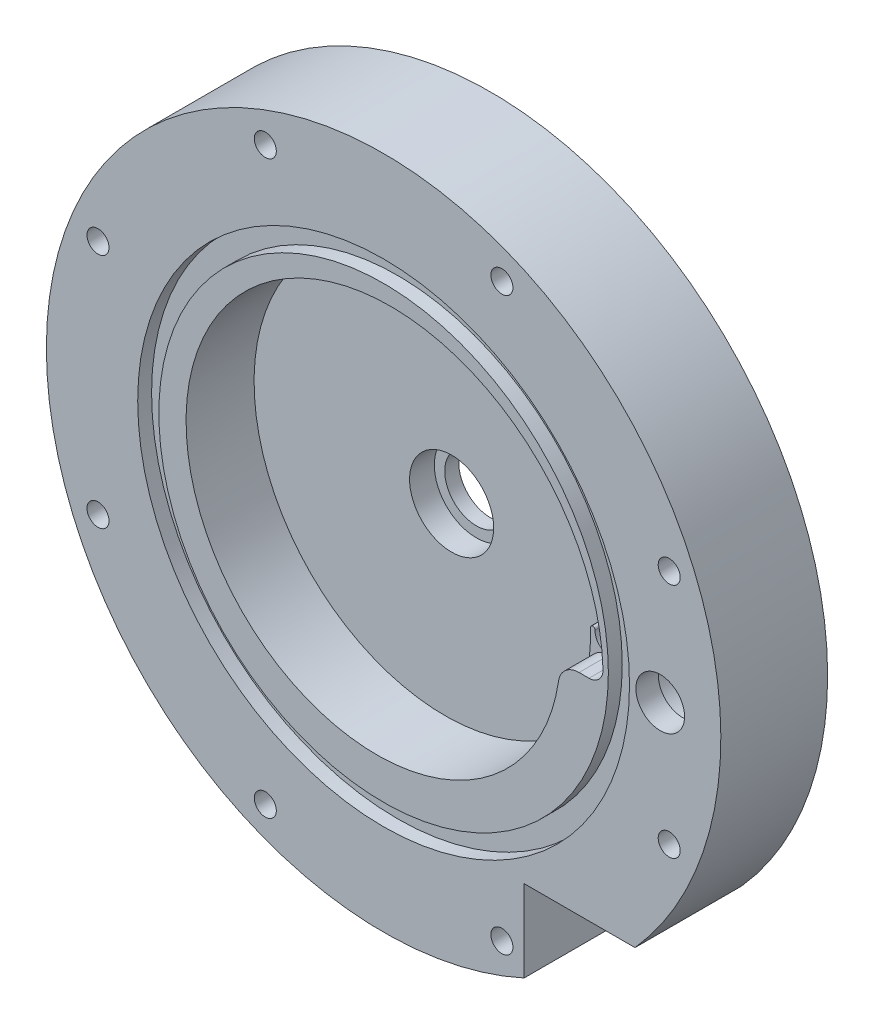
SolidWorks part; units mm, degrees
material "6061-T6 (SS)"
ref_plane "Front Plane" through (0, 0, 0) normal (0, 0, 1) x (1, 0, 0)
ref_plane "Top Plane" through (0, 0, 0) normal (0, 1, 0) x (1, 0, 0)
ref_plane "Right Plane" through (0, 0, 0) normal (1, 0, 0) x (0, 0, -1)
sketch "Sketch22" plane through (0, 0, 0) normal (0, 1, 0) x (1, 0, 0)
  line L0 (-25.4, 0) -> (-9.5, 0)
  line L1 (-25.4, 0) -> (-25.4, -15.367)
  line L3 (-25.4, -15.367) -> (-76.2, -15.367)
  line L4 (-76.2, -15.367) -> (-76.2, 8.763)
  line L5 (-9.5, 0) -> (-9.5, 5.588)
  line L7 (-9.5, 5.588) -> (-7.1437, 5.588)
  line L8 (-7.1437, 5.588) -> (-7.1437, 8.763)
  line L9 (-7.1437, 8.763) -> (-76.2, 8.763)
  line L10 (0, 0) -> (0, 9.525) construction
  dimension "D1" = 14.2875
  dimension "D2" = 19
  dimension "D4" = 3.175
  dimension "D5" = 50.8
  dimension "D6" = 152.4
  dimension "D7" = 24.13
  dimension ".27" = 5.588
revolve "Main Body" add sketch "Sketch22" angle 360 about L10
curve "Volute Spiral"
sketch "Sketch23" plane through (0, 0, 0) normal (0, 0, 1) x (1, 0, 0)
  line L0 (44.1669, -3.2789) -> (46.41, -3.2789)
  arc A1 (40.9936, 0) -> (44.1669, -3.2789) centre (44.1669, -0.1039) ccw
  arc A2 (39.9395, 0) -> (40.9936, 0) centre (40.4666, 0.0173) cw
  arc A4 (46.41, -3.2789) -> (49.578, 0) centre (46.41, -0.1091) ccw
  spline S0 degree 3 poles (2036.7889, 105.1389) (27.9917, 30.1612) (39.5671, 15.0372) (39.954, -0.5026) (39.9588, -0.7541) (39.9652, -1.2573) (39.9616, -2.517) (39.8751, -4.3652) (39.6495, -6.5428) (39.3399, -8.5438) (38.9295, -10.5302) (38.4188, -12.497) (37.8089, -14.4391) (37.1009, -16.3516) (36.2962, -18.2293) (35.3965, -20.0675) (34.4038, -21.8614) (33.3202, -23.6061) (32.1481, -25.2972) (30.8902, -26.9301) (29.5494, -28.5005) (28.1288, -30.0042) (26.6317, -31.4371) (25.0616, -32.7952) (23.4223, -34.075) (21.7176, -35.2728) (19.9517, -36.3854) (18.1288, -37.4095) (16.2533, -38.3423) (14.3299, -39.1811) (12.3632, -39.9234) (10.3581, -40.5669) (8.3195, -41.1098) (6.2525, -41.5501) (4.1622, -41.8865) (2.054, -42.1178) (-0.0671, -42.2429) (-2.1955, -42.2611) (-4.3259, -42.1721) (-6.4529, -41.9757) (-8.5711, -41.6719) (-10.675, -41.2613) (-12.7593, -40.7443) (-14.8186, -40.1221) (-16.8476, -39.3958) (-18.841, -38.5668) (-20.7936, -37.6369) (-22.7003, -36.6081) (-24.5561, -35.4827) (-26.3561, -34.2632) (-28.0956, -32.9524) (-29.7698, -31.5532) (-31.3743, -30.0689) (-32.9048, -28.503) (-34.357, -26.8593) (-35.7272, -25.1415) (-37.0114, -23.3537) (-38.2061, -21.5004) (-39.308, -19.586) (-40.314, -17.615) (-41.221, -15.5925) (-42.0265, -13.5232) (-42.7281, -11.4123) (-43.3237, -9.265) (-43.8112, -7.0867) (-44.1892, -4.8828) (-44.4563, -2.6588) (-44.6113, -0.4202) (-44.6537, 1.8272) (-44.5827, 4.0778) (-44.3982, 6.3259) (-44.1003, 8.5657) (-43.6894, 10.7916) (-43.1661, 12.9978) (-42.5313, 15.1786) (-41.7863, 17.3284) (-40.9326, 19.4417) (-39.9719, 21.5129) (-38.9064, 23.5366) (-37.7384, 25.5075) (-36.4705, 27.4204) (-35.1055, 29.2703) (-33.6468, 31.0522) (-32.0975, 32.7613) (-30.4614, 34.3932) (-28.7423, 35.9432) (-26.9442, 37.4073) (-25.0716, 38.7814) (-23.1289, 40.0617) (-21.1208, 41.2447) (-19.0521, 42.3269) (-16.928, 43.3053) (-14.7537, 44.177) (-12.5345, 44.9396) (-10.2758, 45.5905) (-7.9834, 46.1279) (-5.6629, 46.55) (-3.3202, 46.8552) (-0.9611, 47.0425) (1.4085, 47.1109) (3.7826, 47.06) (6.155, 46.8893) (8.5199, 46.5989) (10.8711, 46.1892) (13.2026, 45.6608) (15.5084, 45.0146) (17.7826, 44.252) (20.0193, 43.3744) (22.2127, 42.3836) (24.357, 41.2819) (26.4467, 40.0717) (28.4762, 38.7556) (30.4402, 37.3367) (32.3334, 35.8182) (34.1508, 34.2036) (35.8876, 32.4968) (37.539, 30.7018) (39.1006, 28.8228) (40.568, 26.8643) (41.9373, 24.8311) (43.2047, 22.7281) (44.3665, 20.5604) (45.4195, 18.3333) (46.3606, 16.0523) (47.1871, 13.7229) (47.8965, 11.351) (48.4866, 8.9424) (48.9555, 6.5032) (49.2727, 4.2452) (49.431, 2.5929) (49.4967, 1.6609) (49.522, 1.2461) (49.539, 0.9348) (49.554, 0.6234) (50.3116, -17.2348) (38.9556, -35.4442) (2048.9371, 22.4075) knots -0.163415 -0.163415 -0.163415 -0.163415 0.000895 0.001791 0.002687 0.003583 0.007168 0.016147 0.023344 0.030554 0.037776 0.045012 0.05226 0.059521 0.066796 0.074083 0.081383 0.088697 0.096023 0.103362 0.110715 0.118081 0.12546 0.132852 0.140257 0.147676 0.155108 0.162553 0.170011 0.177483 0.184968 0.192466 0.199978 0.207503 0.215042 0.222594 0.230159 0.237738 0.245331 0.252937 0.260556 0.268189 0.275836 0.283496 0.291169 0.298857 0.306558 0.314272 0.322 0.329742 0.337497 0.345267 0.353049 0.360846 0.368656 0.37648 0.384318 0.39217 0.400035 0.407914 0.415807 0.423714 0.431634 0.439569 0.447517 0.455479 0.463455 0.471445 0.479449 0.487467 0.495499 0.503544 0.511604 0.519677 0.527765 0.535867 0.543982 0.552112 0.560256 0.568413 0.576585 0.584771 0.592971 0.601185 0.609413 0.617655 0.625911 0.634182 0.642466 0.650765 0.659078 0.667405 0.675747 0.684102 0.692472 0.700856 0.709254 0.717666 0.726093 0.734534 0.742989 0.751459 0.759943 0.768441 0.776953 0.78548 0.794021 0.802577 0.811146 0.819731 0.828329 0.836942 0.845569 0.854211 0.862867 0.871538 0.880223 0.888922 0.897636 0.906365 0.915108 0.923865 0.932637 0.941423 0.950224 0.95904 0.967869 0.976714 0.985573 0.992227 0.994447 0.995557 0.996667 0.997778 0.998889 1.187662 1.187662 1.187662 1.187662 only from (39.9395, 0) to (49.578, 0) construction
  spline S1 degree 3 poles (39.9395, 0) (39.9423, -0.0837) (39.9478, -0.2513) (39.954, -0.5026) (39.9588, -0.7541) (39.9652, -1.2573) (39.9616, -2.517) (39.8751, -4.3652) (39.6495, -6.5428) (39.3399, -8.5438) (38.9295, -10.5302) (38.4188, -12.497) (37.8089, -14.4391) (37.1009, -16.3516) (36.2962, -18.2293) (35.3965, -20.0675) (34.4038, -21.8614) (33.3202, -23.6061) (32.1481, -25.2972) (30.8902, -26.9301) (29.5494, -28.5005) (28.1288, -30.0042) (26.6317, -31.4371) (25.0616, -32.7952) (23.4223, -34.075) (21.7176, -35.2728) (19.9517, -36.3854) (18.1288, -37.4095) (16.2533, -38.3423) (14.3299, -39.1811) (12.3632, -39.9234) (10.3581, -40.5669) (8.3195, -41.1098) (6.2525, -41.5501) (4.1622, -41.8865) (2.054, -42.1178) (-0.0671, -42.2429) (-2.1955, -42.2611) (-4.3259, -42.1721) (-6.4529, -41.9757) (-8.5711, -41.6719) (-10.675, -41.2613) (-12.7593, -40.7443) (-14.8186, -40.1221) (-16.8476, -39.3958) (-18.841, -38.5668) (-20.7936, -37.6369) (-22.7003, -36.6081) (-24.5561, -35.4827) (-26.3561, -34.2632) (-28.0956, -32.9524) (-29.7698, -31.5532) (-31.3743, -30.0689) (-32.9048, -28.503) (-34.357, -26.8593) (-35.7272, -25.1415) (-37.0114, -23.3537) (-38.2061, -21.5004) (-39.308, -19.586) (-40.314, -17.615) (-41.221, -15.5925) (-42.0265, -13.5232) (-42.7281, -11.4123) (-43.3237, -9.265) (-43.8112, -7.0867) (-44.1892, -4.8828) (-44.4563, -2.6588) (-44.6113, -0.4202) (-44.6537, 1.8272) (-44.5827, 4.0778) (-44.3982, 6.3259) (-44.1003, 8.5657) (-43.6894, 10.7916) (-43.1661, 12.9978) (-42.5313, 15.1786) (-41.7863, 17.3284) (-40.9326, 19.4417) (-39.9719, 21.5129) (-38.9064, 23.5366) (-37.7384, 25.5075) (-36.4705, 27.4204) (-35.1055, 29.2703) (-33.6468, 31.0522) (-32.0975, 32.7613) (-30.4614, 34.3932) (-28.7423, 35.9432) (-26.9442, 37.4073) (-25.0716, 38.7814) (-23.1289, 40.0617) (-21.1208, 41.2447) (-19.0521, 42.3269) (-16.928, 43.3053) (-14.7537, 44.177) (-12.5345, 44.9396) (-10.2758, 45.5905) (-7.9834, 46.1279) (-5.6629, 46.55) (-3.3202, 46.8552) (-0.9611, 47.0425) (1.4085, 47.1109) (3.7826, 47.06) (6.155, 46.8893) (8.5199, 46.5989) (10.8711, 46.1892) (13.2026, 45.6608) (15.5084, 45.0146) (17.7826, 44.252) (20.0193, 43.3744) (22.2127, 42.3836) (24.357, 41.2819) (26.4467, 40.0717) (28.4762, 38.7556) (30.4402, 37.3367) (32.3334, 35.8182) (34.1508, 34.2036) (35.8876, 32.4968) (37.539, 30.7018) (39.1006, 28.8228) (40.568, 26.8643) (41.9373, 24.8311) (43.2047, 22.7281) (44.3665, 20.5604) (45.4195, 18.3333) (46.3606, 16.0523) (47.1871, 13.7229) (47.8965, 11.351) (48.4866, 8.9424) (48.9555, 6.5032) (49.2727, 4.2452) (49.431, 2.5929) (49.4967, 1.6609) (49.522, 1.2461) (49.539, 0.9348) (49.554, 0.6234) (49.5673, 0.3117) (49.5744, 0.1039) (49.578, 0) knots 0 0 0 0 0.000895 0.001791 0.002687 0.003583 0.007168 0.016147 0.023344 0.030554 0.037776 0.045012 0.05226 0.059521 0.066796 0.074083 0.081383 0.088697 0.096023 0.103362 0.110715 0.118081 0.12546 0.132852 0.140257 0.147676 0.155108 0.162553 0.170011 0.177483 0.184968 0.192466 0.199978 0.207503 0.215042 0.222594 0.230159 0.237738 0.245331 0.252937 0.260556 0.268189 0.275836 0.283496 0.291169 0.298857 0.306558 0.314272 0.322 0.329742 0.337497 0.345267 0.353049 0.360846 0.368656 0.37648 0.384318 0.39217 0.400035 0.407914 0.415807 0.423714 0.431634 0.439569 0.447517 0.455479 0.463455 0.471445 0.479449 0.487467 0.495499 0.503544 0.511604 0.519677 0.527765 0.535867 0.543982 0.552112 0.560256 0.568413 0.576585 0.584771 0.592971 0.601185 0.609413 0.617655 0.625911 0.634182 0.642466 0.650765 0.659078 0.667405 0.675747 0.684102 0.692472 0.700856 0.709254 0.717666 0.726093 0.734534 0.742989 0.751459 0.759943 0.768441 0.776953 0.78548 0.794021 0.802577 0.811146 0.819731 0.828329 0.836942 0.845569 0.854211 0.862867 0.871538 0.880223 0.888922 0.897636 0.906365 0.915108 0.923865 0.932637 0.941423 0.950224 0.95904 0.967869 0.976714 0.985573 0.992227 0.994447 0.995557 0.996667 0.997778 0.998889 1 1 1 1
  dimension "D1" = 3.175
  dimension "D2" = 1.0541
extrude "Volute Cut" cut sketch "Sketch23" along normal through all
ref_plane "Volute Height Plane" through (0, 0, 8.5827) normal (0, 0, 1) x (1, 0, 0)
sketch "Sketch25" plane through (0, 0, 8.5827) normal (0, 0, 1) x (1, 0, 0)
  arc A0 (44.1669, -3.2789) -> (39.5302, -7.28) centre (44.1669, -7.9661) ccw
  arc A1 (46.41, -3.2789) -> (49.578, 0) centre (46.41, -0.1091) ccw construction
  arc A2 (46.41, -3.2789) -> (49.578, 0) centre (46.41, -0.1091) ccw
  arc A3 (40.9936, 0) -> (39.9395, 0) centre (40.4666, 0.0173) ccw construction
  arc A4 (40.9936, 0) -> (44.1669, -3.2789) centre (44.1669, -0.1039) ccw construction
  arc A5 (40.9936, 0) -> (39.9395, 0) centre (40.4666, 0.0173) ccw
  arc A6 (40.9936, 0) -> (44.1669, -3.2789) centre (44.1669, -0.1039) ccw
  spline S1 degree 3 poles (2048.8734, 22.4056) (38.9558, -35.4438) (50.3115, -17.2346) (49.554, 0.6234) (49.539, 0.9348) (49.522, 1.2461) (49.4967, 1.6609) (49.431, 2.5929) (49.2727, 4.2452) (48.9555, 6.5032) (48.4866, 8.9424) (47.8965, 11.351) (47.1871, 13.7229) (46.3606, 16.0523) (45.4195, 18.3333) (44.3665, 20.5604) (43.2047, 22.7281) (41.9373, 24.8311) (40.568, 26.8643) (39.1006, 28.8228) (37.539, 30.7018) (35.8876, 32.4968) (34.1508, 34.2036) (32.3334, 35.8182) (30.4402, 37.3367) (28.4762, 38.7556) (26.4467, 40.0717) (24.357, 41.2819) (22.2127, 42.3836) (20.0193, 43.3744) (17.7826, 44.252) (15.5084, 45.0146) (13.2026, 45.6608) (10.8711, 46.1892) (8.5199, 46.5989) (6.155, 46.8893) (3.7826, 47.06) (1.4085, 47.1109) (-0.9611, 47.0425) (-3.3202, 46.8552) (-5.6629, 46.55) (-7.9834, 46.1279) (-10.2758, 45.5905) (-12.5345, 44.9396) (-14.7537, 44.177) (-16.928, 43.3053) (-19.0521, 42.3269) (-21.1208, 41.2447) (-23.1289, 40.0617) (-25.0716, 38.7814) (-26.9442, 37.4073) (-28.7423, 35.9432) (-30.4614, 34.3932) (-32.0975, 32.7613) (-33.6468, 31.0522) (-35.1055, 29.2703) (-36.4705, 27.4204) (-37.7384, 25.5075) (-38.9064, 23.5366) (-39.9719, 21.5129) (-40.9326, 19.4417) (-41.7863, 17.3284) (-42.5313, 15.1786) (-43.1661, 12.9978) (-43.6894, 10.7916) (-44.1003, 8.5657) (-44.3982, 6.3259) (-44.5827, 4.0778) (-44.6537, 1.8272) (-44.6113, -0.4202) (-44.4563, -2.6588) (-44.1892, -4.8828) (-43.8112, -7.0867) (-43.3237, -9.265) (-42.7281, -11.4123) (-42.0265, -13.5232) (-41.221, -15.5925) (-40.314, -17.615) (-39.308, -19.586) (-38.2061, -21.5004) (-37.0114, -23.3537) (-35.7272, -25.1415) (-34.357, -26.8593) (-32.9048, -28.503) (-31.3743, -30.0689) (-29.7698, -31.5532) (-28.0956, -32.9524) (-26.3561, -34.2632) (-24.5561, -35.4827) (-22.7003, -36.6081) (-20.7936, -37.6369) (-18.841, -38.5668) (-16.8476, -39.3958) (-14.8186, -40.1221) (-12.7593, -40.7443) (-10.675, -41.2613) (-8.5711, -41.6719) (-6.4529, -41.9757) (-4.3259, -42.1721) (-2.1955, -42.2611) (-0.0671, -42.2429) (2.054, -42.1178) (4.1622, -41.8865) (6.2525, -41.5501) (8.3195, -41.1098) (10.3581, -40.5669) (12.3632, -39.9234) (14.3299, -39.1811) (16.2533, -38.3423) (18.1288, -37.4095) (19.9517, -36.3854) (21.7176, -35.2728) (23.4223, -34.075) (25.0616, -32.7952) (26.6317, -31.4371) (28.1288, -30.0042) (29.5494, -28.5005) (30.8902, -26.9301) (32.1481, -25.2972) (33.3202, -23.6061) (34.4038, -21.8614) (35.3965, -20.0675) (36.2962, -18.2293) (37.1009, -16.3516) (37.8089, -14.4391) (38.4188, -12.497) (38.9295, -10.5302) (39.3399, -8.5438) (39.6495, -6.5428) (39.8751, -4.3652) (39.9616, -2.517) (39.9652, -1.2573) (39.9588, -0.7541) (39.954, -0.5026) (39.5671, 15.0364) (27.9928, 30.1597) (2036.501, 105.1281) knots -0.18766 -0.18766 -0.18766 -0.18766 0.001111 0.002222 0.003333 0.004443 0.005553 0.007773 0.014427 0.023286 0.032131 0.04096 0.049776 0.058577 0.067363 0.076135 0.084892 0.093635 0.102364 0.111078 0.119777 0.128462 0.137133 0.145789 0.154431 0.163058 0.171671 0.180269 0.188854 0.197423 0.205979 0.21452 0.223047 0.231559 0.240057 0.248541 0.257011 0.265466 0.273907 0.282334 0.290746 0.299144 0.307528 0.315898 0.324253 0.332595 0.340922 0.349235 0.357534 0.365818 0.374089 0.382345 0.390587 0.398815 0.407029 0.415229 0.423415 0.431587 0.439744 0.447888 0.456018 0.464133 0.472235 0.480323 0.488396 0.496456 0.504501 0.512533 0.520551 0.528555 0.536545 0.544521 0.552483 0.560431 0.568366 0.576286 0.584193 0.592086 0.599965 0.60783 0.615682 0.62352 0.631344 0.639154 0.646951 0.654733 0.662503 0.670258 0.678 0.685728 0.693442 0.701143 0.708831 0.716504 0.724164 0.731811 0.739444 0.747063 0.754669 0.762262 0.769841 0.777406 0.784958 0.792497 0.800022 0.807534 0.815032 0.822517 0.829989 0.837447 0.844892 0.852324 0.859743 0.867148 0.87454 0.881919 0.889285 0.896638 0.903977 0.911303 0.918617 0.925917 0.933204 0.940479 0.94774 0.954988 0.962224 0.969446 0.976656 0.983853 0.992832 0.996417 0.997313 0.998209 0.999105 1.163407 1.163407 1.163407 1.163407 only from (49.578, 0) to (39.9395, 0) construction
  spline S2 degree 3 poles (49.578, 0) (49.5744, 0.1039) (49.5673, 0.3117) (49.554, 0.6234) (49.539, 0.9348) (49.522, 1.2461) (49.4967, 1.6609) (49.431, 2.5929) (49.2727, 4.2452) (48.9555, 6.5032) (48.4866, 8.9424) (47.8965, 11.351) (47.1871, 13.7229) (46.3606, 16.0523) (45.4195, 18.3333) (44.3665, 20.5604) (43.2047, 22.7281) (41.9373, 24.8311) (40.568, 26.8643) (39.1006, 28.8228) (37.539, 30.7018) (35.8876, 32.4968) (34.1508, 34.2036) (32.3334, 35.8182) (30.4402, 37.3367) (28.4762, 38.7556) (26.4467, 40.0717) (24.357, 41.2819) (22.2127, 42.3836) (20.0193, 43.3744) (17.7826, 44.252) (15.5084, 45.0146) (13.2026, 45.6608) (10.8711, 46.1892) (8.5199, 46.5989) (6.155, 46.8893) (3.7826, 47.06) (1.4085, 47.1109) (-0.9611, 47.0425) (-3.3202, 46.8552) (-5.6629, 46.55) (-7.9834, 46.1279) (-10.2758, 45.5905) (-12.5345, 44.9396) (-14.7537, 44.177) (-16.928, 43.3053) (-19.0521, 42.3269) (-21.1208, 41.2447) (-23.1289, 40.0617) (-25.0716, 38.7814) (-26.9442, 37.4073) (-28.7423, 35.9432) (-30.4614, 34.3932) (-32.0975, 32.7613) (-33.6468, 31.0522) (-35.1055, 29.2703) (-36.4705, 27.4204) (-37.7384, 25.5075) (-38.9064, 23.5366) (-39.9719, 21.5129) (-40.9326, 19.4417) (-41.7863, 17.3284) (-42.5313, 15.1786) (-43.1661, 12.9978) (-43.6894, 10.7916) (-44.1003, 8.5657) (-44.3982, 6.3259) (-44.5827, 4.0778) (-44.6537, 1.8272) (-44.6113, -0.4202) (-44.4563, -2.6588) (-44.1892, -4.8828) (-43.8112, -7.0867) (-43.3237, -9.265) (-42.7281, -11.4123) (-42.0265, -13.5232) (-41.221, -15.5925) (-40.314, -17.615) (-39.308, -19.586) (-38.2061, -21.5004) (-37.0114, -23.3537) (-35.7272, -25.1415) (-34.357, -26.8593) (-32.9048, -28.503) (-31.3743, -30.0689) (-29.7698, -31.5532) (-28.0956, -32.9524) (-26.3561, -34.2632) (-24.5561, -35.4827) (-22.7003, -36.6081) (-20.7936, -37.6369) (-18.841, -38.5668) (-16.8476, -39.3958) (-14.8186, -40.1221) (-12.7593, -40.7443) (-10.675, -41.2613) (-8.5711, -41.6719) (-6.4529, -41.9757) (-4.3259, -42.1721) (-2.1955, -42.2611) (-0.0671, -42.2429) (2.054, -42.1178) (4.1622, -41.8865) (6.2525, -41.5501) (8.3195, -41.1098) (10.3581, -40.5669) (12.3632, -39.9234) (14.3299, -39.1811) (16.2533, -38.3423) (18.1288, -37.4095) (19.9517, -36.3854) (21.7176, -35.2728) (23.4223, -34.075) (25.0616, -32.7952) (26.6317, -31.4371) (28.1288, -30.0042) (29.5494, -28.5005) (30.8902, -26.9301) (32.1481, -25.2972) (33.3202, -23.6061) (34.4038, -21.8614) (35.3965, -20.0675) (36.2962, -18.2293) (37.1009, -16.3516) (37.8089, -14.4391) (38.4188, -12.497) (38.9295, -10.5302) (39.3399, -8.5438) (39.6495, -6.5428) (39.8751, -4.3652) (39.9616, -2.517) (39.9652, -1.2573) (39.9588, -0.7541) (39.954, -0.5026) (39.9478, -0.2513) (39.9423, -0.0837) (39.9395, 0) knots 0 0 0 0 0.001111 0.002222 0.003333 0.004443 0.005553 0.007773 0.014427 0.023286 0.032131 0.04096 0.049776 0.058577 0.067363 0.076135 0.084892 0.093635 0.102364 0.111078 0.119777 0.128462 0.137133 0.145789 0.154431 0.163058 0.171671 0.180269 0.188854 0.197423 0.205979 0.21452 0.223047 0.231559 0.240057 0.248541 0.257011 0.265466 0.273907 0.282334 0.290746 0.299144 0.307528 0.315898 0.324253 0.332595 0.340922 0.349235 0.357534 0.365818 0.374089 0.382345 0.390587 0.398815 0.407029 0.415229 0.423415 0.431587 0.439744 0.447888 0.456018 0.464133 0.472235 0.480323 0.488396 0.496456 0.504501 0.512533 0.520551 0.528555 0.536545 0.544521 0.552483 0.560431 0.568366 0.576286 0.584193 0.592086 0.599965 0.60783 0.615682 0.62352 0.631344 0.639154 0.646951 0.654733 0.662503 0.670258 0.678 0.685728 0.693442 0.701143 0.708831 0.716504 0.724164 0.731811 0.739444 0.747063 0.754669 0.762262 0.769841 0.777406 0.784958 0.792497 0.800022 0.807534 0.815032 0.822517 0.829989 0.837447 0.844892 0.852324 0.859743 0.867148 0.87454 0.881919 0.889285 0.896638 0.903977 0.911303 0.918617 0.925917 0.933204 0.940479 0.94774 0.954988 0.962224 0.969446 0.976656 0.983853 0.992832 0.996417 0.997313 0.998209 0.999105 1 1 1 1
extrude "Cap Cut" cut sketch "Sketch25" along normal through all contours A2 S2 A5 A6 | S2 A6 A5 region at (40.8724, -2.704, 8.5827)
sketch "Sketch28" plane through (0, 0, 15.367) normal (0, 0, 1) x (1, 0, 0)
  line L1 (31.75, -69.2703) -> (56.7961, -69.2703)
  line L2 (31.75, -69.2703) -> (31.75, -50.8)
  line L3 (31.75, -50.8) -> (56.7961, -50.8)
  line L4 (56.7961, -69.2703) -> (56.7961, -50.8)
  circle A0 centre (0, 0) radius 76.2 construction
  dimension "D1" = 50.8
  dimension "D2" = 31.75
extrude "Outlet Hole Cut" cut sketch "Sketch28" against normal through all
hole_wizard "Outlet Hole" positions "3DSketch2" profile "Sketch20" hole size "3/8" standard "ANSI Inch"
sketch3d "3DSketch2"
  line L0 (46.41, -3.2789, 0) -> (44.1669, -3.2789, 8.5827) construction
  point P0 (45.2885, -3.2789, 4.2913)
  point P11 (45.2885, -3.2789, 4.2913)
  point P20 (45.2885, -3.2789, 4.2913)
  point P22 (45.2885, -50.8, 4.2913)
sketch "Sketch20" plane through (45.2885, -50.8, 4.2913) normal (1, 0, 0) x (0, 0, -1)
  line L0 (0, 0) -> (0, 53.6616)
  line L1 (0, 53.6616) -> (4.7625, 50.8)
  line L2 (4.7625, 50.8) -> (4.7625, 0)
  line L5 (4.7625, 0) -> (0, 0)
  line L10 (0, 53.6616) -> (-4.7625, 50.8) construction
  line L11 (0, -6.35) -> (0, 107.95) construction
  dimension "Hole Dia." = 9.525
  dimension "Hole Depth" = 50.8
  dimension "Drill Angle" = 118
hole_wizard "Outlet Pipe Thread" positions "3DSketch3" profile "Sketch21" hole size "3/8" standard "ANSI Inch"
sketch3d "3DSketch3"
  line L0 (40.526, -50.8, 4.2913) -> (50.051, -50.8, 4.2913) construction
  line L2 (45.2885, -50.8, -0.4712) -> (45.2885, -50.8, 9.0538) construction
  circle A4 centre (45.2885, -50.8, 4.2913) radius 4.7625 construction
  point P2 (45.2885, -50.8, 4.2913)
  point P38 (45.2885, -55.5625, 4.2913)
sketch "Sketch21" plane through (45.2885, -50.8, 4.2913) normal (1, 0, 0) x (0, 0, -1)
  line L0 (0, 0) -> (0, 16.9886)
  line L1 (0, 16.9886) -> (7.1374, 12.7)
  line L2 (7.1374, 12.7) -> (7.1374, 0)
  line L5 (7.1374, 0) -> (0, 0)
  line L10 (0, 16.9886) -> (-7.1374, 12.7) construction
  line L11 (0, -6.35) -> (0, 107.95) construction
  dimension "Hole Dia." = 14.2748
  dimension "Hole Depth" = 12.7
  dimension "Drill Angle" = 118
sketch "Sketch26" plane through (0, 0, 15.367) normal (0, 0, 1) x (1, 0, 0)
  line L0 (64.533, -26.7304) -> (70.3996, -29.1605) construction
  line L1 (76.2, 0) -> (0, 0) construction
  circle A0 centre (64.533, -26.7304) radius 2.4892
  circle A1 centre (0, 0) radius 76.2 construction
  dimension "D1" = 4.9784
  dimension "D2" = 6.35
  dimension "D3" = 22.5
extrude "Fastener Hole" cut sketch "Sketch26" against normal through all
pattern_circular "Fastener Holes" count 8 over 360 about axis through (0, 0, 0) along (0, 0, 1) of "Fastener Hole"
ref_axis "Axis1" through (0, 0, -8.763) along (0, 0, 1)
ref_plane "Plane1" through (0, 0, 0) normal (0, 1, 0) x (0, 0, 1)
sketch "Sketch16" plane through (0, 0, 15.367) normal (0, 0, 1) x (1, 0, 0)
  circle A0 centre (0, 0) radius 50.7873
  circle A1 centre (0, 0) radius 55.5625
  dimension "D1" = 4.7752
  dimension "D2" = 111.125
extrude "O-Ring Groove" cut sketch "Sketch16" against normal blind 3.1369
sketch "Sketch27" plane through (0, 0, 0) normal (0, 1, 0) x (0, 0, 1)
  line L1 (3.937, 70.4375) -> (10.287, 70.4375)
  line L2 (-8.763, 76.2) -> (-8.763, -76.2) construction
  line L3 (-8.763, 73.676) -> (3.937, 73.676)
  line L4 (3.937, 73.676) -> (3.937, 70.4375)
  line L8 (10.287, 54.5625) -> (3.937, 54.5625)
  line L9 (3.937, 54.5625) -> (3.937, 51.324)
  line L10 (3.937, 51.324) -> (-8.763, 51.324)
  line L12 (15.367, 62.5) -> (-8.763, 62.5)
  line L13 (-8.763, 73.676) -> (-8.763, 51.324)
  line L14 (10.287, 70.4375) -> (10.287, 68)
  line L15 (10.287, 68) -> (15.367, 68)
  line L16 (15.367, 68) -> (15.367, 57)
  line L17 (15.367, 57) -> (10.287, 57)
  line L18 (10.287, 57) -> (10.287, 54.5625)
  line L19 (15.367, -55.5625) -> (15.367, 55.5625) construction
  dimension "D1" = 6.35
  dimension "D2" = 22.352
  dimension "D3" = 62.5
  dimension "D4" = 12.7
  dimension "D5" = 15.875
  dimension "D6" = 11
revolve "Turbine Shaft Hole" cut sketch "Sketch27" angle 360 about L12 region at (57.6425, 0, 1.6995)
hole_wizard "Tap Drill for #10-32 Tap1" positions "3DSketch4" profile "Sketch30" hole size "#10-32" standard "ANSI Inch"
sketch3d "3DSketch4"
  line L0 (64.533, 26.7304, -8.763) -> (52.7997, 21.8704, -8.763) construction
  line L1 (64.533, 26.7304, -8.763) -> (64.533, 26.7304, 15.367) construction
  line L3 (52.7997, 21.8704, -8.763) -> (0, 0, -8.763) construction
  point P0 (52.7997, 21.8704, -8.763)
  dimension "D1" = 57.15
sketch "Sketch30" plane through (52.7997, 21.8704, -8.763) normal (1, 0, 0) x (0, 1, 0)
  line L0 (0, 0) -> (0, 13.9133)
  line L1 (0, 13.9133) -> (2.0193, 12.7)
  line L2 (2.0193, 12.7) -> (2.0193, 0)
  line L5 (2.0193, 0) -> (0, 0)
  line L10 (0, 13.9133) -> (-2.0193, 12.7) construction
  line L11 (0, -6.35) -> (0, 107.95) construction
  dimension "Hole Dia." = 4.0386
  dimension "Hole Depth" = 12.7
  dimension "Drill Angle" = 118
pattern_circular "CirPattern1" count 8 over 360 about axis through (0, 0, 0) along (0, 0, 1) of "Tap Drill for #10-32 Tap1" reverse direction yes
